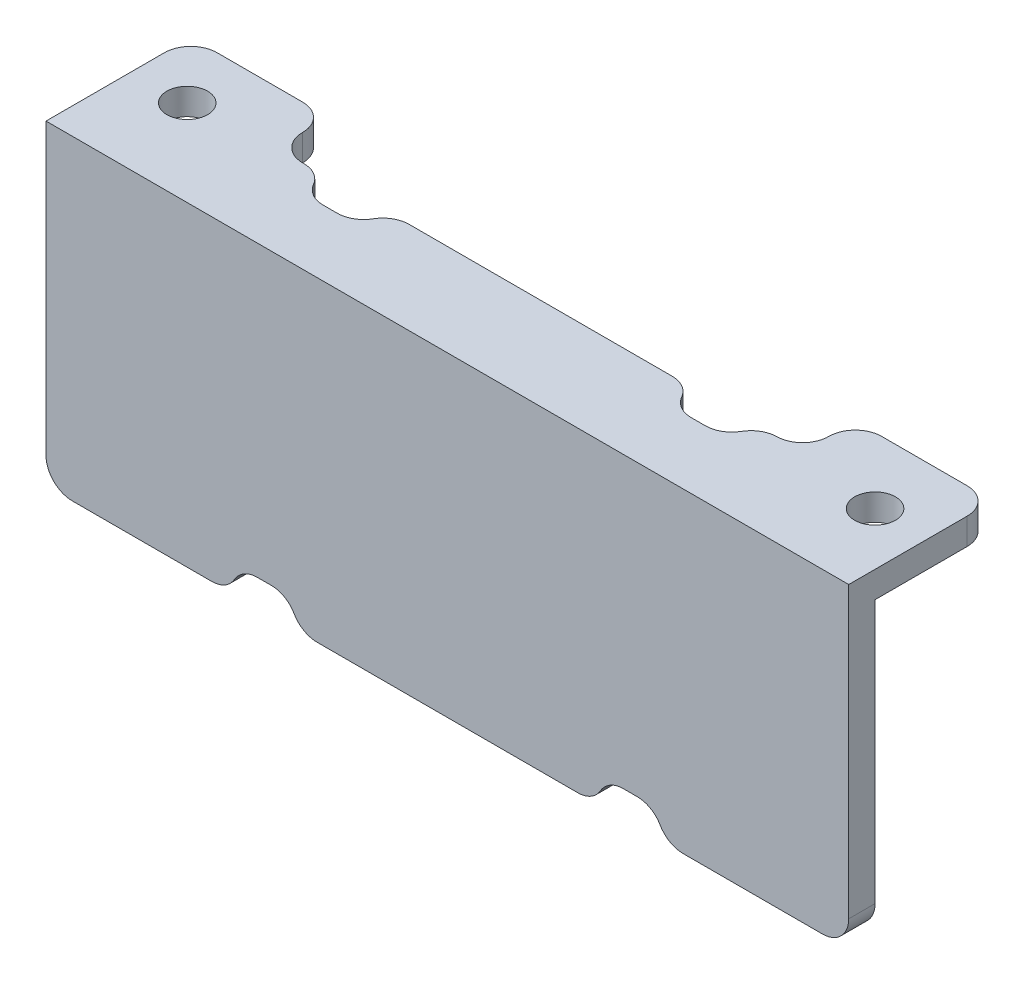
SolidWorks part; units mm, degrees
material "PET"
ref_plane "Front" through (0, 0, 0) normal (0, 0, 1) x (1, 0, 0)
ref_plane "Top" through (0, 0, 0) normal (0, 1, 0) x (1, 0, 0)
ref_plane "Right" through (0, 0, 0) normal (1, 0, 0) x (0, 0, -1)
sketch "Sketch1" plane through (0, 0, 0) normal (1, 0, 0) x (0, 0, -1)
  line L0 (0, 0) -> (-3.175, 0)
  line L1 (-3.175, 0) -> (-3.175, 38.1)
  line L2 (-3.175, 38.1) -> (14.2875, 38.1)
  line L3 (14.2875, 38.1) -> (14.2875, 34.925)
  line L4 (14.2875, 34.925) -> (0, 34.925)
  line L5 (0, 34.925) -> (0, 0)
  dimension "D1" = 3.175
  dimension "D2" = 14.2875
  dimension "D3" = 38.1
extrude "Boss-Extrude1" add sketch "Sketch1" against normal mid plane 96.8375
sketch "Sketch6" plane through (0, 34.925, 0) normal (0, -1, 0) x (-1, 0, 0)
  line L0 (48.4187, 0) -> (48.4187, 14.2875) construction
  line L1 (48.4187, 14.2875) -> (-48.4187, 14.2875) construction
  line L2 (-48.4187, 0) -> (-48.4187, 14.2875) construction
  point P0 (41.7949, 7.239)
  point P3 (-42.0688, 6.35)
  dimension "D1" = 6.6238
  dimension "D2" = 7.0485
  dimension "D3" = 6.35
  dimension "D4" = 7.9375
hole_wizard "#10 (0.1935) Diameter Hole1" positions "Sketch6" profile "Sketch5" hole size "#10" standard "ANSI Inch" end condition up to next
sketch "Sketch5" plane through (-41.7949, 34.925, -7.239) normal (1, 0, 0) x (0, 0, -1)
  line L0 (0, 0) -> (0, 3.175)
  line L1 (0, 3.175) -> (2.4574, 3.175)
  line L2 (2.4574, 3.175) -> (2.4574, 0)
  line L5 (2.4574, 0) -> (0, 0)
  line L11 (0, -6.35) -> (0, 107.95) construction
  dimension "Thru Hole Dia." = 4.9149
  dimension "Thru Hole Depth" = 3.175
sketch "Sketch9" plane through (0, 38.1, 0) normal (0, 1, 0) x (1, 0, 0)
  line L0 (-48.4187, 14.2875) -> (48.4187, 14.2875) construction
  line L1 (-31.75, 14.2875) -> (31.75, 14.2875)
  line L2 (-31.75, 14.2875) -> (-31.75, 7.9375)
  line L3 (-31.75, 7.9375) -> (31.75, 7.9375)
  line L4 (31.75, 14.2875) -> (31.75, 7.9375)
  line L5 (-31.75, 11.1125) -> (-48.4187, 11.1125) construction
  line L6 (-48.4187, 14.2875) -> (-48.4187, -3.175) construction
  line L7 (31.75, 11.1125) -> (48.4187, 11.1125) construction
  line L8 (48.4187, 14.2875) -> (48.4187, -3.175) construction
  dimension "D1" = 6.35
  dimension "D2" = 63.5
extrude "Cut-Extrude3" cut sketch "Sketch9" against normal up to next
sketch "Sketch7" plane through (0, 0, 3.175) normal (0, 0, 1) x (1, 0, 0)
  line L0 (-48.4187, 0) -> (48.4187, 0) construction
  line L1 (-18.9007, 0) -> (-25.2507, 0)
  line L2 (-18.9007, 0) -> (-18.9007, 3.175)
  line L3 (-18.9007, 3.175) -> (-25.2507, 3.175)
  line L4 (-25.2507, 0) -> (-25.2507, 3.175)
  line L6 (18.9007, 0) -> (25.2507, 0)
  line L7 (18.9007, 0) -> (18.9007, 3.175)
  line L8 (18.9007, 3.175) -> (25.2507, 3.175)
  line L9 (25.2507, 0) -> (25.2507, 3.175)
  line L11 (-48.4187, 38.1) -> (-48.4187, 0) construction
  line L12 (48.4187, 38.1) -> (48.4187, 0) construction
  dimension "D1" = 23.1681
  dimension "D2" = 6.35
  dimension "D3" = 23.1681
  dimension "D4" = 3.175
extrude "Cut-Extrude1" cut sketch "Sketch7" against normal up to next
sketch "Sketch8" plane through (0, 38.1, 0) normal (0, 1, 0) x (1, 0, 0)
  line L1 (-25.2468, 7.9375) -> (-18.8968, 7.9375)
  line L2 (-25.2468, 7.9375) -> (-25.2468, 4.7625)
  line L3 (-25.2468, 4.7625) -> (-18.8968, 4.7625)
  line L4 (-18.8968, 7.9375) -> (-18.8968, 4.7625)
  line L5 (-31.75, 7.9375) -> (31.75, 7.9375) construction
  line L6 (19.1707, 7.9375) -> (25.5207, 7.9375)
  line L7 (19.1707, 7.9375) -> (19.1707, 4.7625)
  line L8 (19.1707, 4.7625) -> (25.5207, 4.7625)
  line L9 (25.5207, 7.9375) -> (25.5207, 4.7625)
  circle A0 centre (-41.7949, 7.239) radius 2.4574 construction
  circle A1 centre (42.0688, 6.35) radius 2.4574 construction
  dimension "D3" = 16.5481
  dimension "D1" = 3.175
  dimension "D2" = 6.35
  dimension "D4" = 16.5481
extrude "Cut-Extrude2" cut sketch "Sketch8" against normal up to next
fillet "Fillet1" radius 3.175 14 edges at (25.2507, 0, 1.5875) (18.9007, 0, 1.5875) (-18.9007, 0, 1.5875) (-25.2507, 0, 1.5875) (48.4187, 36.5125, -14.2875) (-48.4187, 36.5125, -14.2875) (48.4187, 0, 1.5875) (-48.4187, 0, 1.5875) (25.5207, 36.5125, -7.9375) (19.1707, 36.5125, -7.9375) (-18.8968, 36.5125, -7.9375) (-25.2468, 36.5125, -7.9375) (31.75, 36.5125, -14.2875) (-31.75, 36.5125, -14.2875)
fillet "Fillet2" radius 3.175 10 edges at (25.2507, 3.175, 1.5875) (18.9007, 3.175, 1.5875) (-18.9007, 3.175, 1.5875) (-25.2507, 3.175, 1.5875) (25.5207, 36.5125, -4.7625) (19.1707, 36.5125, -4.7625) (-18.8968, 36.5125, -4.7625) (-25.2468, 36.5125, -4.7625) (-31.75, 36.5125, -7.9375) (31.75, 36.5125, -7.9375)
